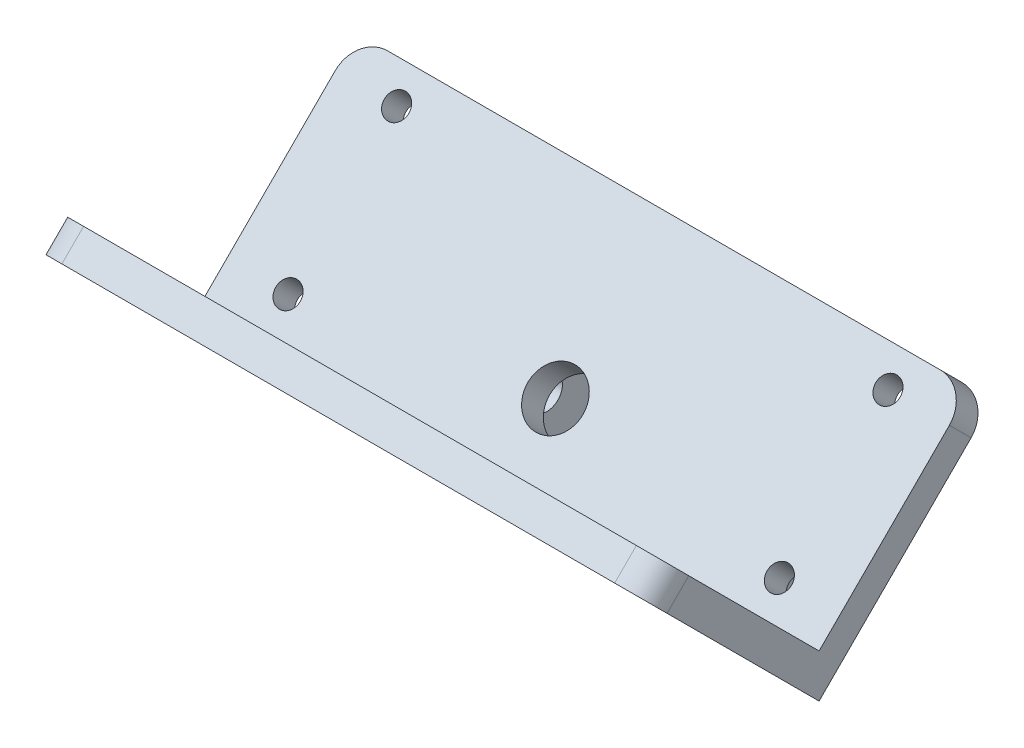
SolidWorks part; units mm, degrees
other "Title Block Table1"
other "DetailItem1"
material "PA Type 6 - Black"
ref_plane "Front Plane" through (0, 0, 0) normal (0, 0, 1) x (1, 0, 0)
ref_plane "Top Plane" through (0, 0, 0) normal (0, 1, 0) x (1, 0, 0)
ref_plane "Right Plane" through (0, 0, 0) normal (1, 0, 0) x (0, 0, -1)
ref_axis "X-Axis" through (-55, 0, 0) along (1, 0, 0)
ref_axis "Y-Axis" through (0, 20.0187, 0) along (0, -1, 0)
ref_axis "Z-Axis" through (0, 0, -46.5091) along (0, 0, 1)
sketch "Sketch2" plane through (0, 0, 0) normal (1, 0, 0) x (0, 0, -1)
  line L0 (0, 0) -> (-24.7487, 24.7487)
  line L2 (24.7487, 24.7487) -> (0, 0)
  line L3 (0, -7.0711) -> (-28.2843, 21.2132)
  line L5 (28.2843, 21.2132) -> (0, -7.0711)
  line L6 (0, 0) -> (-19.1751, 19.1751) construction
  line L7 (40.7053, 40.7053) -> (0, 0) construction
  line L8 (-19.1751, 19.1751) -> (40.7053, 40.7053) construction
  line L10 (-28.2843, 21.2132) -> (60.0425, 52.9715) construction
  line L11 (0, 0) -> (0, -29.9276) construction
  line L12 (-28.2843, 21.2132) -> (-24.7487, 24.7487)
  line L17 (24.7487, 24.7487) -> (28.2843, 21.2132)
  line L18 (60.0425, 52.9715) -> (0, -7.0711) construction
  dimension "D1" = 5
  dimension "D2" = 40
  dimension "D3" = 40
extrude "Boss-Extrude1" add sketch "Sketch2" along normal mid plane 100
hole_wizard "M8 Clearance Hole1" positions "Sketch5" profile "Sketch6" hole size "M8" standard "DIN" end condition through all
sketch "Sketch5" plane through (0, 0, 0) normal (0, 0.7071, 0.7071) x (1, 0, 0)
  line L1 (-15, 25) -> (15, 25) construction
  line L2 (-15, 25) -> (-15, -5) construction
  line L3 (-15, -5) -> (15, -5) construction
  line L4 (15, 25) -> (15, -5) construction
  line L5 (-15, 25) -> (15, -5) construction
  line L6 (-15, -5) -> (15, 25) construction
  line L7 (0, 10) -> (0, -5) construction
  line L9 (50, -5) -> (-50, -5) construction
  point P0 (0, 10)
  point P4 (0, 10)
  dimension "D1" = 30
  dimension "D2" = 15
sketch "Sketch6" plane through (0, 7.0711, -7.0711) normal (1, 0, 0) x (0, -0.7071, 0.7071)
  line L0 (0, 0) -> (0, 25)
  line L1 (0, 25) -> (4.5, 25)
  line L2 (4.5, 25) -> (4.5, 0)
  line L5 (4.5, 0) -> (0, 0)
  line L11 (0, -6.35) -> (0, 107.95) construction
  dimension "Thru Hole Dia." = 9
  dimension "Thru Hole Depth" = 25
sketch "Sketch7" plane through (0, -3.5355, -3.5355) normal (0, -0.7071, -0.7071) x (1, 0, 0)
  line L0 (50, 5) -> (-50, 5) construction
  line L1 (15.5, 5) -> (20.5, 5)
  line L2 (15.5, 5) -> (15.5, -25)
  line L3 (15.5, -25) -> (20.5, -25)
  line L4 (20.5, 5) -> (20.5, -25)
  line L5 (15.5, 5) -> (-15.5, -25) construction
  line L6 (-15.5, 5) -> (-20.5, 5)
  line L7 (-15.5, 5) -> (-15.5, -25)
  line L8 (-15.5, -25) -> (-20.5, -25)
  line L9 (-20.5, 5) -> (-20.5, -25)
  line L10 (-15.5, -25) -> (15.5, -25) construction
  line L11 (-15.5, 5) -> (15.5, -25) construction
  point P10 (0, -10)
  point P11 (0, -10)
  dimension "D1" = 31
  dimension "D2" = 5
extrude "Boss-Extrude4" add sketch "Sketch7" along normal blind 30
sketch "Sketch9" plane through (20.5, 0, 0) normal (1, 0, 0) x (0, 0, -1)
  line L0 (0, -7.0711) -> (21.2132, -7.0711) construction
  line L2 (21.2132, -7.0711) -> (42.4264, -7.0711) construction
  line L3 (42.4264, -7.0711) -> (21.2132, -28.2843) construction
  circle A0 centre (21.2132, -7.0711) radius 2.5
  dimension "D1" = 5
extrude "Cut-Extrude1" cut sketch "Sketch9" against normal through all
sketch "Sketch11" plane through (0, 0, 0) normal (0, 0.7071, 0.7071) x (1, 0, 0)
  line L0 (0, 17.5) -> (0, 0) construction
  line L1 (-40, 30) -> (40, 30) construction
  line L2 (-40, 30) -> (-40, 5) construction
  line L3 (-40, 5) -> (40, 5) construction
  line L4 (40, 30) -> (40, 5) construction
  line L5 (-40, 30) -> (40, 5) construction
  line L6 (-40, 5) -> (40, 30) construction
  line L7 (50, 35) -> (-50, 35) construction
  line L8 (50, 0) -> (-50, 0) construction
  circle A0 centre (-40, 30) radius 2
  circle A1 centre (-40, 5) radius 2
  circle A2 centre (40, 30) radius 2
  circle A3 centre (40, 5) radius 2
  point P4 (0, 17.5)
  dimension "D1" = 4
  dimension "D2" = 80
  dimension "D3" = 5
  dimension "D4" = 5
extrude "Cut-Extrude2" cut sketch "Sketch11" against normal through all
mirror "Mirror1" about plane through (0, 0, 0) normal (0, 0, 1) of "Cut-Extrude2"
sketch "Sketch12" plane through (0, -3.5355, 3.5355) normal (0, 0.7071, -0.7071) x (1, 0, 0)
  line L0 (-50, 5) -> (-20.5, 35)
  line L5 (-20.5, 35) -> (-20.5, 5)
  line L6 (-20.5, 5) -> (-50, 5)
  line L7 (20.5, 5) -> (20.5, 35)
  line L8 (20.5, 35) -> (50, 5)
  line L9 (50, 5) -> (20.5, 5)
  line L10 (50, 5) -> (50, 0) construction
  line L11 (15.5, 35) -> (20.5, 35) construction
  point P0 (20.5, 5)
extrude "Boss-Extrude7" add sketch "Sketch12" along normal blind 5
fillet "Fillet4" radius 5 6 edges at (18, -7.0711, -42.4264) (-18, -7.0711, -42.4264) (-50, 22.981, -26.5165) (-50, 22.981, 26.5165) (50, 22.981, -26.5165) (50, 22.981, 26.5165)
